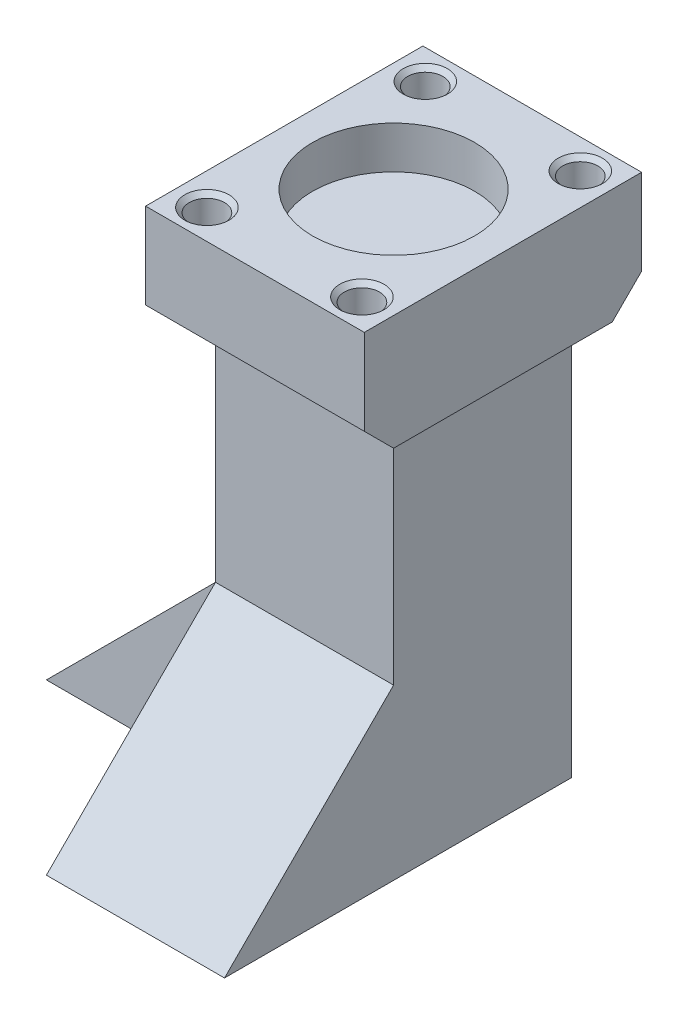
SolidWorks part; units mm, degrees
material "ABS"
ref_plane "Front Plane" through (0, 0, 0) normal (0, 0, 1) x (1, 0, 0)
ref_plane "Top Plane" through (0, 0, 0) normal (0, 1, 0) x (1, 0, 0)
ref_plane "Right Plane" through (0, 0, 0) normal (1, 0, 0) x (0, 0, -1)
sketch "Sketch1" plane through (0, 0, 0) normal (0, 1, 0) x (1, 0, 0)
  line L1 (-10.033, 10.033) -> (10.033, 10.033)
  line L2 (-10.033, 10.033) -> (-10.033, -10.033)
  line L3 (-10.033, -10.033) -> (10.033, -10.033)
  line L4 (10.033, 10.033) -> (10.033, -10.033)
  dimension "D1" = 20.066
  dimension "D2" = 20.066
  dimension "D3" = 10.033
  dimension "D4" = 10.033
extrude "Boss-Extrude1" add sketch "Sketch1" along normal blind 57.404
sketch "Sketch2" plane through (0, 57.404, 0) normal (0, 1, 0) x (1, 0, 0)
  line L0 (-10.033, 10.033) -> (-10.033, -10.033) construction
  line L1 (10.033, -10.033) -> (-10.033, -10.033)
  line L2 (10.033, -10.033) -> (10.033, 10.033)
  line L3 (10.033, 10.033) -> (-10.033, 10.033)
  line L4 (-10.033, -10.033) -> (-10.033, 10.033)
  line L6 (12.319, -15.621) -> (-12.319, -15.621)
  line L7 (12.319, -15.621) -> (12.319, 15.621)
  line L8 (12.319, 15.621) -> (-12.319, 15.621)
  line L9 (-12.319, -15.621) -> (-12.319, 15.621)
  dimension "D1" = 31.242
  dimension "D2" = 24.638
  dimension "D3" = 2.286
  dimension "D4" = 5.588
extrude "Boss-Extrude2" add sketch "Sketch2" against normal blind 15.24
sketch "Sketch9" plane through (10.033, 0, 0) normal (1, 0, 0) x (0, 0, -1)
  line L0 (-10.033, 0) -> (-29.083, 0)
  line L1 (-29.083, 0) -> (-10.033, 19.05)
  line L2 (-10.033, 42.164) -> (-10.033, 0) construction
  line L3 (-10.033, 0) -> (-10.033, 19.05)
  dimension "D1" = 19.05
  dimension "D2" = 19.05
extrude "Boss-Extrude3" add sketch "Sketch9" against normal blind 20.066
sketch "Sketch10" plane through (0, 0, -10.033) normal (0, 0, -1) x (-1, 0, 0)
  line L0 (10.033, 0) -> (29.083, 0)
  line L1 (29.083, 0) -> (10.033, 19.05)
  line L2 (10.033, 42.164) -> (10.033, 0) construction
  line L3 (10.033, 19.05) -> (10.033, 0)
  dimension "D1" = 19.05
  dimension "D2" = 19.05
extrude "Boss-Extrude4" add sketch "Sketch10" against normal blind 20.066
sketch "Sketch11" plane through (0, 0, 0) normal (0, -1, 0) x (-1, 0, 0)
  line L6 (-10.033, 10.033) -> (29.083, 10.033) construction
  line L7 (10.033, -10.033) -> (10.033, -29.083) construction
  line L9 (10.033, -29.083) -> (-10.033, -29.083) construction
  line L10 (29.083, -10.033) -> (29.083, 10.033) construction
  line L11 (-10.033, -29.083) -> (-10.033, 10.033) construction
  point P0 (18.923, 0)
  point P1 (0, -18.923)
  point P10 (-3.683, 3.683)
  dimension "D1" = 10.033
  dimension "D2" = 10.033
  dimension "D3" = 10.16
  dimension "D4" = 10.16
  dimension "D5" = 6.35
  dimension "D6" = 6.35
hole_wizard "CBORE for #4 Socket Head Cap Screw2" positions "Sketch13" profile "Sketch12" counterbore size "#4" standard "ANSI Inch"
sketch "Sketch13" plane through (0, 0, 0) normal (0, -1, 0) x (-1, 0, 0)
  point P0 (0, -18.923)
  point P6 (18.923, 0)
  point P11 (0, 0)
sketch "Sketch12" plane through (0, 0, 18.923) normal (1, 0, 0) x (0, 0, -1)
  line L0 (0, 0) -> (0, 8.9181)
  line L1 (0, 8.9181) -> (1.6319, 7.9375)
  line L2 (1.6319, 7.9375) -> (1.6319, 4.7625)
  line L3 (1.6319, 4.7625) -> (1.9844, 4.7625)
  line L4 (1.9844, 4.7625) -> (1.9844, 0)
  line L5 (1.9844, 0) -> (0, 0)
  line L10 (0, 8.9181) -> (-1.632, 7.9375) construction
  line L11 (0, -6.35) -> (0, 107.95) construction
  dimension "Hole Dia." = 3.2639
  dimension "Hole Depth" = 7.9375
  dimension "C'Bore Dia." = 3.9688
  dimension "C'Bore Depth" = 4.7625
  dimension "Drill Angle" = 118
sketch "Sketch17" plane through (0, 57.404, 0) normal (0, 1, 0) x (1, 0, 0)
  line L0 (12.319, -15.621) -> (12.319, 15.621) construction
  line L2 (-12.319, -15.621) -> (12.319, -15.621) construction
  line L4 (-12.319, 15.621) -> (-12.319, -15.621) construction
  line L5 (12.319, 15.621) -> (-12.319, 15.621) construction
  point P0 (8.636, 12.192)
  point P1 (8.636, -12.192)
  point P2 (-8.636, -12.192)
  point P3 (-8.636, 12.192)
  dimension "D1" = 3.683
  dimension "D2" = 3.429
  dimension "D3" = 3.429
  dimension "D4" = 3.683
  dimension "D5" = 3.683
  dimension "D6" = 3.429
  dimension "D7" = 3.429
  dimension "D8" = 3.683
hole_wizard "CBORE for #4 Socket Head Cap Screw4" positions "Sketch19" profile "Sketch18" counterbore size "#4" standard "ANSI Inch"
sketch "Sketch19" plane through (0, 57.404, 0) normal (0, 1, 0) x (1, 0, 0)
  line L2 (8.7312, 12.3031) -> (-8.7313, 12.3031)
  line L3 (8.7312, 12.3031) -> (8.7313, -12.3031)
  line L4 (8.7313, -12.3031) -> (-8.7312, -12.3031)
  line L5 (-8.7313, 12.3031) -> (-8.7312, -12.3031)
  line L6 (8.7312, 12.3031) -> (-8.7312, -12.3031) construction
  line L7 (8.7313, -12.3031) -> (-8.7313, 12.3031) construction
  line L13 (0.2513, 12.5555) -> (0.2513, 15.621) construction
  line L14 (12.319, 15.621) -> (-12.319, 15.621) construction
  line L16 (0, -12.3031) -> (0, -15.621) construction
  line L17 (-12.319, -15.621) -> (12.319, -15.621) construction
  line L20 (12.319, 0) -> (8.7312, 0) construction
  line L21 (12.319, -15.621) -> (12.319, 15.621) construction
  line L23 (-8.7312, 0) -> (-12.319, 0) construction
  line L24 (-12.319, 15.621) -> (-12.319, -15.621) construction
  point P91 (-8.7312, -12.3031)
  point P174 (8.7312, 12.3031)
  point P175 (8.7313, -12.3031)
  point P176 (-8.7313, 12.3031)
  dimension "D1" = 24.6062
  dimension "D2" = 17.4625
sketch "Sketch18" plane through (-8.7312, 57.404, 12.3031) normal (1, 0, 0) x (0, 0, 1)
  line L0 (0, 0) -> (0, 10.5691)
  line L1 (0, 10.5691) -> (1.6319, 9.5885)
  line L2 (1.6319, 9.5885) -> (1.6319, 4.7625)
  line L3 (1.6319, 4.7625) -> (1.9844, 4.7625)
  line L4 (1.9844, 4.7625) -> (1.9844, 0)
  line L5 (1.9844, 0) -> (0, 0)
  line L10 (0, 10.5691) -> (-1.632, 9.5885) construction
  line L11 (0, -6.35) -> (0, 107.95) construction
  dimension "Hole Dia." = 3.2639
  dimension "Hole Depth" = 9.5885
  dimension "C'Bore Dia." = 3.9688
  dimension "C'Bore Depth" = 4.7625
  dimension "Drill Angle" = 118
chamfer "Chamfer5" distance 0.508 angle 45 7 edges at (0, 0, 16.9386) (-18.923, 0, -1.9844) (0, 0, -1.9844) (-8.7312, 57.404, 14.2875) (-8.7313, 57.404, -10.3188) (8.7313, 57.404, 14.2875) (8.7312, 57.404, -10.3188)
chamfer "Chamfer6" distance 2.286 angle 45 2 edges at (12.319, 42.164, 0) (-12.319, 42.164, 0)
chamfer "Chamfer7" distance 5.588 angle 45 2 edges at (0, 42.164, 15.621) (0, 42.164, -15.621)
sketch "Sketch20" plane through (0, 57.404, 0) normal (0, 1, 0) x (1, 0, 0)
  circle A0 centre (0, 0) radius 9.1281
  dimension "D1" = 18.2562
extrude "Cut-Extrude1" cut sketch "Sketch20" against normal blind 4.7625
